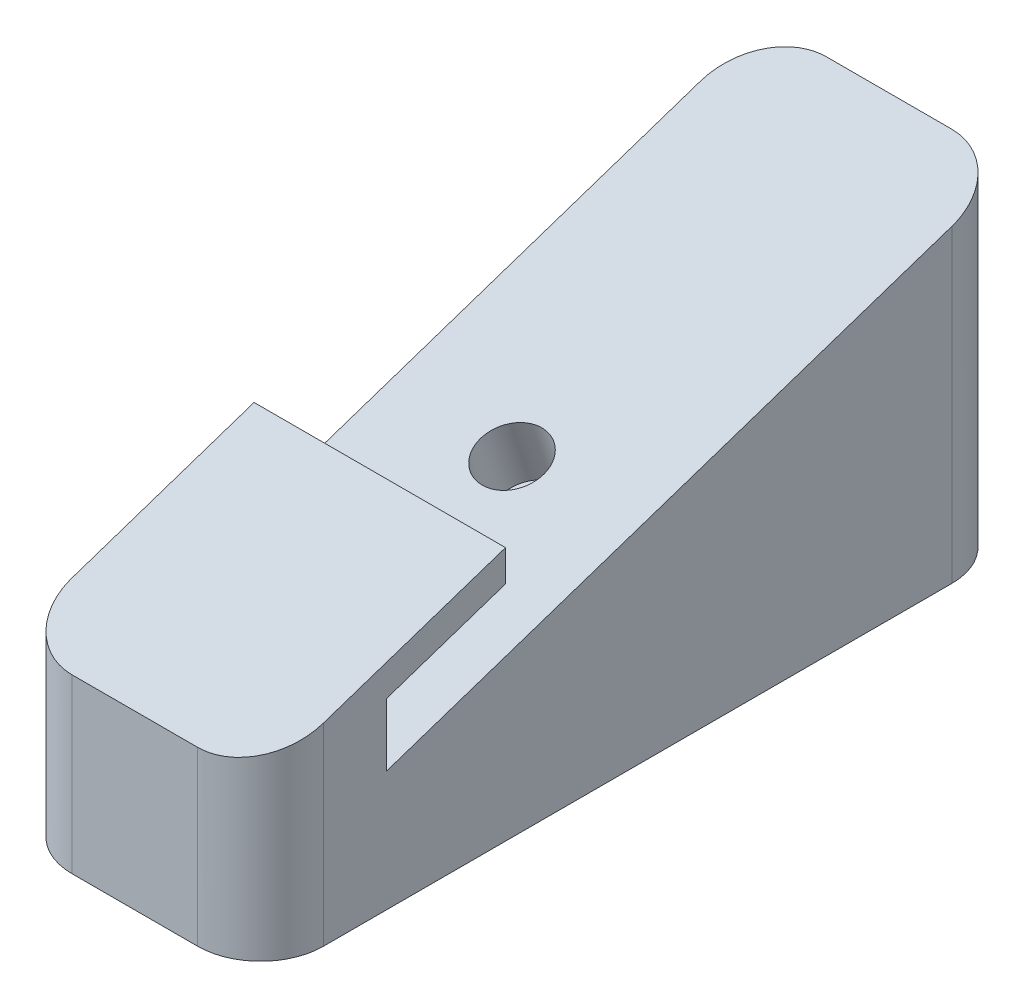
SolidWorks part; units mm, degrees
material "ABS"
ref_plane "Front Plane" through (0, 0, 0) normal (0, 0, 1) x (1, 0, 0)
ref_plane "Top Plane" through (0, 0, 0) normal (0, 1, 0) x (1, 0, 0)
ref_plane "Right Plane" through (0, 0, 0) normal (1, 0, 0) x (0, 0, -1)
sketch "Sketch1" plane through (0, 0, 0) normal (0, 1, 0) x (1, 0, 0)
  line L0 (-12.7, -25.4) -> (12.7, -25.4)
  line L1 (-12.7, -38.1) -> (12.7, -38.1)
  line L2 (-12.7, -38.1) -> (-12.7, 38.1)
  line L3 (-12.7, 38.1) -> (12.7, 38.1)
  line L4 (12.7, -38.1) -> (12.7, 38.1)
  line L5 (-12.7, -38.1) -> (12.7, 38.1) construction
  line L6 (-12.7, 38.1) -> (12.7, -38.1) construction
  point P0 (0, 0)
  dimension "D3" = 12.7
  dimension "D1" = 25.4
  dimension "D2" = 76.2
extrude "Boss-Extrude1" add sketch "Sketch1" along normal blind 33.3756 contours L1 L4 L0 L2 | L0 L4 L3 L2 region at (0, 0, -6.35) region at (0, 0, 31.75)
sketch "Sketch4" plane through (12.7, 0, 0) normal (1, 0, 0) x (0, 0, -1)
  line L0 (38.1, 33.3756) -> (-38.1, 33.3756)
  line L1 (-38.1, 33.3756) -> (-38.1, 7.8794)
  line L3 (-38.1, 7.8794) -> (38.1, 33.3756)
  line L4 (-38.1, 7.8794) -> (38.0791, 7.8794) construction
  line L6 (-38.1, 33.3756) -> (-38.1, 0) construction
  dimension "D1" = 18.5
extrude "Cut-Extrude2" cut sketch "Sketch4" against normal through all both and the other way through all
sketch "Sketch5" plane through (0, 18.5507, 6.207) normal (0, 0.9483, 0.3173) x (1, 0, 0)
  line L0 (0, 46.7214) -> (0, -33.6309) construction
  line L1 (12.7, 46.7214) -> (-12.7, 46.7214) construction
  line L2 (-12.7, -33.6309) -> (12.7, -33.6309) construction
  line L3 (-12.7, 6.5452) -> (12.7, 6.5452) construction
  line L4 (-12.7, -33.6309) -> (-12.7, 46.7214) construction
  line L5 (12.7, 46.7214) -> (12.7, -33.6309) construction
  circle A0 centre (0, 6.5452) radius 3.175
  dimension "D1" = 6.35
extrude "Cut-Extrude3" cut sketch "Sketch5" against normal blind 6.35
ref_point "Point1"
extrude "Boss-Extrude2" add sketch "Sketch1<5>" along normal blind 9.525 from surface contours L1 L4 L0 L2 region at (0, 0, 31.75) starting at face at (0, 19.6201, 3.0109)
sketch "Sketch1<5>" plane through (0, 0, 0) normal (0, 1, 0) x (1, 0, 0) same geometry as "Sketch1"
sketch "Sketch7" plane through (0, 0, 25.4) normal (0, 0, -1) x (-1, 0, 0)
  line L1 (-12.7, 21.6538) -> (12.7, 21.6538)
  line L2 (-12.7, 21.6538) -> (-12.7, 18.4788)
  line L3 (-12.7, 18.4788) -> (12.7, 18.4788)
  line L4 (12.7, 21.6538) -> (12.7, 18.4788)
  line L5 (12.7, 21.6538) -> (12.7, 12.1288) construction
  dimension "D1" = 3.175
extrude "Boss-Extrude3" add sketch "Sketch7" along direction (0, 0.3173, -0.9483) on the side of the normal blind 12.7
fillet "Fillet1" radius 6.35 4 edges at (-12.7, 16.6878, -38.1) (-12.7, 8.7022, 38.1) (12.7, 8.7022, 38.1)
